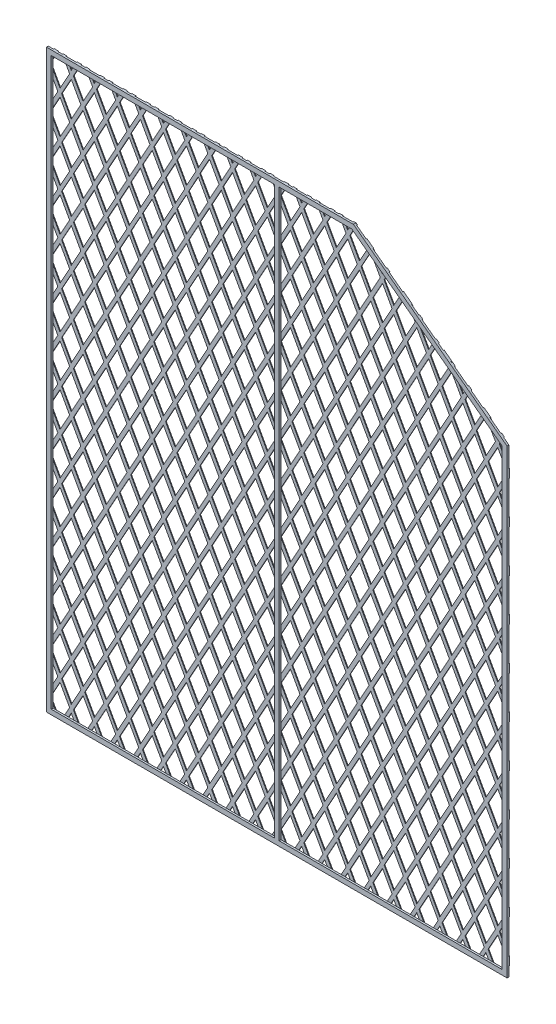
SolidWorks part; units mm, degrees
material "Acero inoxidable fundido"
ref_plane "Alzado" through (0, 0, 0) normal (0, 0, 1) x (1, 0, 0)
ref_plane "Planta" through (0, 0, 0) normal (0, 1, 0) x (1, 0, 0)
ref_plane "Vista lateral" through (0, 0, 0) normal (1, 0, 0) x (0, 0, -1)
sketch "Croquis1" plane through (0, 0, 0) normal (0, 0, 1) x (1, 0, 0)
  line L17 (0, 0) -> (0, 1500)
  line L18 (0, 1500) -> (800, 1500)
  line L19 (800, 1500) -> (1200, 1200)
  line L20 (1200, 1200) -> (1200, 0)
  line L21 (1200, 0) -> (0, 0)
  line L22 (12.7, 12.7) -> (12.7, 1487.3)
  line L23 (12.7, 1487.3) -> (593.65, 1487.3)
  line L24 (795.7667, 1487.3) -> (1187.3, 1193.65)
  line L25 (1187.3, 1193.65) -> (1187.3, 12.7)
  line L26 (1187.3, 12.7) -> (606.35, 12.7)
  line L27 (593.65, 12.7) -> (593.65, 1487.3)
  line L28 (606.35, 12.7) -> (606.35, 1487.3)
  line L29 (593.65, 12.7) -> (12.7, 12.7)
  line L30 (1187.3, 12.7) -> (12.7, 12.7) construction
  line L31 (606.35, 1487.3) -> (795.7667, 1487.3)
  line L32 (12.7, 1487.3) -> (795.7667, 1487.3) construction
  point P15 (600, 0)
  dimension "D1" = 1500
  dimension "D2" = 1200
  dimension "D3" = 800
  dimension "D4" = 1200
  dimension "D6" = 6.35
  dimension "D7" = 12.7
  dimension "D5" = 12.7
extrude "Saliente-Extruir1" add sketch "Croquis1" along normal blind 4.8
sketch "Croquis2" plane through (0, 0, 0) normal (0, 0, -1) x (-1, 0, 0)
  line L0 (0, 1500) -> (-800, 1500)
  line L1 (-800, 1500) -> (-1200, 1200)
  line L2 (-1200, 1200) -> (-1200, 0)
  line L3 (-1200, 0) -> (0, 0)
  line L4 (0, 0) -> (0, 1500)
extrude "Saliente-Extruir2" add sketch "Croquis2" along normal blind 1.9
sketch "Croquis3" plane through (0, 0, -1.9) normal (0, 0, -1) x (-1, 0, 0)
  line L0 (-600, 0) -> (-600, 1437.8229) construction
  line L1 (-1146.758, 750) -> (0, 750) construction
  line L2 (-600, 795) -> (-575, 750)
  line L3 (-575, 750) -> (-600, 705)
  line L4 (-600, 705) -> (-625, 750)
  line L5 (-625, 750) -> (-600, 795)
  line L10 (-630.7198, 850.2956) -> (-605.7198, 805.2956)
  line L11 (-605.7198, 805.2956) -> (-630.7198, 760.2956)
  line L12 (-630.7198, 760.2956) -> (-655.7198, 805.2956)
  line L13 (-655.7198, 805.2956) -> (-630.7198, 850.2956)
  line L166 (-1200, 0) -> (0, 0) construction
  line L167 (0, 0) -> (0, 1500) construction
  line L168 (-660, 795) -> (-635, 750)
  line L169 (-635, 750) -> (-660, 705)
  line L170 (-660, 705) -> (-685, 750)
  line L171 (-685, 750) -> (-660, 795)
  line L172 (-690.7198, 850.2956) -> (-665.7198, 805.2956)
  line L173 (-665.7198, 805.2956) -> (-690.7198, 760.2956)
  line L174 (-690.7198, 760.2956) -> (-715.7198, 805.2956)
  line L175 (-715.7198, 805.2956) -> (-690.7198, 850.2956)
  line L176 (-720, 795) -> (-695, 750)
  line L177 (-695, 750) -> (-720, 705)
  line L178 (-720, 705) -> (-745, 750)
  line L179 (-745, 750) -> (-720, 795)
  line L180 (-750.7198, 850.2956) -> (-725.7198, 805.2956)
  line L181 (-725.7198, 805.2956) -> (-750.7198, 760.2956)
  line L182 (-750.7198, 760.2956) -> (-775.7198, 805.2956)
  line L183 (-775.7198, 805.2956) -> (-750.7198, 850.2956)
  line L184 (-780, 795) -> (-755, 750)
  line L185 (-755, 750) -> (-780, 705)
  line L186 (-780, 705) -> (-805, 750)
  line L187 (-805, 750) -> (-780, 795)
  line L188 (-810.7198, 850.2956) -> (-785.7198, 805.2956)
  line L189 (-785.7198, 805.2956) -> (-810.7198, 760.2956)
  line L190 (-810.7198, 760.2956) -> (-835.7198, 805.2956)
  line L191 (-835.7198, 805.2956) -> (-810.7198, 850.2956)
  line L192 (-840, 795) -> (-815, 750)
  line L193 (-815, 750) -> (-840, 705)
  line L194 (-840, 705) -> (-865, 750)
  line L195 (-865, 750) -> (-840, 795)
  line L196 (-870.7198, 850.2956) -> (-845.7198, 805.2956)
  line L197 (-845.7198, 805.2956) -> (-870.7198, 760.2956)
  line L198 (-870.7198, 760.2956) -> (-895.7198, 805.2956)
  line L199 (-895.7198, 805.2956) -> (-870.7198, 850.2956)
  line L200 (-900, 795) -> (-875, 750)
  line L201 (-875, 750) -> (-900, 705)
  line L202 (-900, 705) -> (-925, 750)
  line L203 (-925, 750) -> (-900, 795)
  line L204 (-930.7198, 850.2956) -> (-905.7198, 805.2956)
  line L205 (-905.7198, 805.2956) -> (-930.7198, 760.2956)
  line L206 (-930.7198, 760.2956) -> (-955.7198, 805.2956)
  line L207 (-955.7198, 805.2956) -> (-930.7198, 850.2956)
  line L208 (-960, 795) -> (-935, 750)
  line L209 (-935, 750) -> (-960, 705)
  line L210 (-960, 705) -> (-985, 750)
  line L211 (-985, 750) -> (-960, 795)
  line L212 (-990.7198, 850.2956) -> (-965.7198, 805.2956)
  line L213 (-965.7198, 805.2956) -> (-990.7198, 760.2956)
  line L214 (-990.7198, 760.2956) -> (-1015.7198, 805.2956)
  line L215 (-1015.7198, 805.2956) -> (-990.7198, 850.2956)
  line L216 (-1020, 795) -> (-995, 750)
  line L217 (-995, 750) -> (-1020, 705)
  line L218 (-1020, 705) -> (-1045, 750)
  line L219 (-1045, 750) -> (-1020, 795)
  line L220 (-1050.7198, 850.2956) -> (-1025.7198, 805.2956)
  line L221 (-1025.7198, 805.2956) -> (-1050.7198, 760.2956)
  line L222 (-1050.7198, 760.2956) -> (-1075.7198, 805.2956)
  line L223 (-1075.7198, 805.2956) -> (-1050.7198, 850.2956)
  line L224 (-1080, 795) -> (-1055, 750)
  line L225 (-1055, 750) -> (-1080, 705)
  line L226 (-1080, 705) -> (-1105, 750)
  line L227 (-1105, 750) -> (-1080, 795)
  line L228 (-1110.7198, 850.2956) -> (-1085.7198, 805.2956)
  line L229 (-1085.7198, 805.2956) -> (-1110.7198, 760.2956)
  line L230 (-1110.7198, 760.2956) -> (-1135.7198, 805.2956)
  line L231 (-1135.7198, 805.2956) -> (-1110.7198, 850.2956)
  line L232 (-1140, 795) -> (-1115, 750)
  line L233 (-1115, 750) -> (-1140, 705)
  line L234 (-1140, 705) -> (-1165, 750)
  line L235 (-1165, 750) -> (-1140, 795)
  line L236 (-1170.7198, 850.2956) -> (-1145.7198, 805.2956)
  line L237 (-1145.7198, 805.2956) -> (-1170.7198, 760.2956)
  line L238 (-1170.7198, 760.2956) -> (-1195.7198, 805.2956)
  line L239 (-1195.7198, 805.2956) -> (-1170.7198, 850.2956)
  line L240 (-1200, 795) -> (-1175, 750)
  line L241 (-1175, 750) -> (-1200, 705)
  line L242 (-1200, 705) -> (-1225, 750)
  line L243 (-1225, 750) -> (-1200, 795)
  line L244 (-1230.7198, 850.2956) -> (-1205.7198, 805.2956)
  line L245 (-1205.7198, 805.2956) -> (-1230.7198, 760.2956)
  line L246 (-1230.7198, 760.2956) -> (-1255.7198, 805.2956)
  line L247 (-1255.7198, 805.2956) -> (-1230.7198, 850.2956)
  line L248 (-540, 795) -> (-515, 750)
  line L249 (-515, 750) -> (-540, 705)
  line L250 (-540, 705) -> (-565, 750)
  line L251 (-565, 750) -> (-540, 795)
  line L252 (-570.7198, 850.2956) -> (-545.7198, 805.2956)
  line L253 (-545.7198, 805.2956) -> (-570.7198, 760.2956)
  line L254 (-570.7198, 760.2956) -> (-595.7198, 805.2956)
  line L255 (-595.7198, 805.2956) -> (-570.7198, 850.2956)
  line L256 (-480, 795) -> (-455, 750)
  line L257 (-455, 750) -> (-480, 705)
  line L258 (-480, 705) -> (-505, 750)
  line L259 (-505, 750) -> (-480, 795)
  line L260 (-510.7198, 850.2956) -> (-485.7198, 805.2956)
  line L261 (-485.7198, 805.2956) -> (-510.7198, 760.2956)
  line L262 (-510.7198, 760.2956) -> (-535.7198, 805.2956)
  line L263 (-535.7198, 805.2956) -> (-510.7198, 850.2956)
  line L264 (-420, 795) -> (-395, 750)
  line L265 (-395, 750) -> (-420, 705)
  line L266 (-420, 705) -> (-445, 750)
  line L267 (-445, 750) -> (-420, 795)
  line L268 (-450.7198, 850.2956) -> (-425.7198, 805.2956)
  line L269 (-425.7198, 805.2956) -> (-450.7198, 760.2956)
  line L270 (-450.7198, 760.2956) -> (-475.7198, 805.2956)
  line L271 (-475.7198, 805.2956) -> (-450.7198, 850.2956)
  line L272 (-360, 795) -> (-335, 750)
  line L273 (-335, 750) -> (-360, 705)
  line L274 (-360, 705) -> (-385, 750)
  line L275 (-385, 750) -> (-360, 795)
  line L276 (-390.7198, 850.2956) -> (-365.7198, 805.2956)
  line L277 (-365.7198, 805.2956) -> (-390.7198, 760.2956)
  line L278 (-390.7198, 760.2956) -> (-415.7198, 805.2956)
  line L279 (-415.7198, 805.2956) -> (-390.7198, 850.2956)
  line L280 (-300, 795) -> (-275, 750)
  line L281 (-275, 750) -> (-300, 705)
  line L282 (-300, 705) -> (-325, 750)
  line L283 (-325, 750) -> (-300, 795)
  line L284 (-330.7198, 850.2956) -> (-305.7198, 805.2956)
  line L285 (-305.7198, 805.2956) -> (-330.7198, 760.2956)
  line L286 (-330.7198, 760.2956) -> (-355.7198, 805.2956)
  line L287 (-355.7198, 805.2956) -> (-330.7198, 850.2956)
  line L288 (-240, 795) -> (-215, 750)
  line L289 (-215, 750) -> (-240, 705)
  line L290 (-240, 705) -> (-265, 750)
  line L291 (-265, 750) -> (-240, 795)
  line L292 (-270.7198, 850.2956) -> (-245.7198, 805.2956)
  line L293 (-245.7198, 805.2956) -> (-270.7198, 760.2956)
  line L294 (-270.7198, 760.2956) -> (-295.7198, 805.2956)
  line L295 (-295.7198, 805.2956) -> (-270.7198, 850.2956)
  line L296 (-180, 795) -> (-155, 750)
  line L297 (-155, 750) -> (-180, 705)
  line L298 (-180, 705) -> (-205, 750)
  line L299 (-205, 750) -> (-180, 795)
  line L300 (-210.7198, 850.2956) -> (-185.7198, 805.2956)
  line L301 (-185.7198, 805.2956) -> (-210.7198, 760.2956)
  line L302 (-210.7198, 760.2956) -> (-235.7198, 805.2956)
  line L303 (-235.7198, 805.2956) -> (-210.7198, 850.2956)
  line L304 (-120, 795) -> (-95, 750)
  line L305 (-95, 750) -> (-120, 705)
  line L306 (-120, 705) -> (-145, 750)
  line L307 (-145, 750) -> (-120, 795)
  line L308 (-150.7198, 850.2956) -> (-125.7198, 805.2956)
  line L309 (-125.7198, 805.2956) -> (-150.7198, 760.2956)
  line L310 (-150.7198, 760.2956) -> (-175.7198, 805.2956)
  line L311 (-175.7198, 805.2956) -> (-150.7198, 850.2956)
  line L312 (-60, 795) -> (-35, 750)
  line L313 (-35, 750) -> (-60, 705)
  line L314 (-60, 705) -> (-85, 750)
  line L315 (-85, 750) -> (-60, 795)
  line L316 (-90.7198, 850.2956) -> (-65.7198, 805.2956)
  line L317 (-65.7198, 805.2956) -> (-90.7198, 760.2956)
  line L318 (-90.7198, 760.2956) -> (-115.7198, 805.2956)
  line L319 (-115.7198, 805.2956) -> (-90.7198, 850.2956)
  line L320 (0, 795) -> (25, 750)
  line L321 (25, 750) -> (0, 705)
  line L322 (0, 705) -> (-25, 750)
  line L323 (-25, 750) -> (0, 795)
  line L324 (-30.7198, 850.2956) -> (-5.7198, 805.2956)
  line L325 (-5.7198, 805.2956) -> (-30.7198, 760.2956)
  line L326 (-30.7198, 760.2956) -> (-55.7198, 805.2956)
  line L327 (-55.7198, 805.2956) -> (-30.7198, 850.2956)
  point P91 (0, 750)
  point P171 (-600, 0)
  dimension "D1" = 90
  dimension "D2" = 50
  dimension "D3" = 50
  dimension "D4" = 10
  dimension "D5" = 11
  dimension "D6" = 11
extrude "Cortar-Extruir1" cut sketch "Croquis3" against normal blind 1.9
pattern_linear "MatrizL1" count 8 spacing 110 along (0, 1, 0) of "Cortar-Extruir1"
pattern_linear "MatrizL2" count 8 spacing 110 along (0, -1, 0) of "Cortar-Extruir1"
